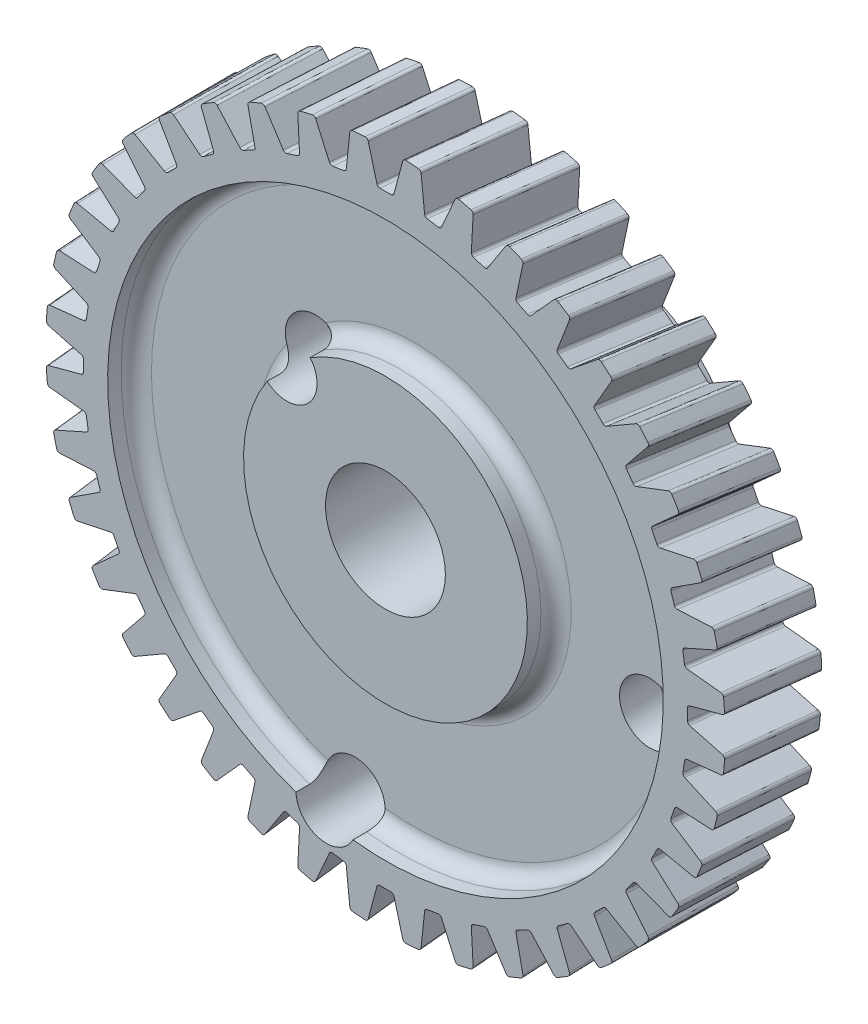
SolidWorks part; units mm, degrees
ref_plane "Front Plane" through (0, 0, 0) normal (0, 0, 1) x (1, 0, 0)
ref_plane "Top Plane" through (0, 0, 0) normal (0, 1, 0) x (1, 0, 0)
ref_plane "Right Plane" through (0, 0, 0) normal (1, 0, 0) x (0, 0, -1)
sketch "Sketch2" plane through (0, 0, 0) normal (1, 0, 0) x (0, 0, -1)
  line L0 (0, 0) -> (0, 22.5) construction
  line L1 (11, 3.9688) -> (-3.2, 3.9687)
  line L2 (-3.2, 3.9687) -> (-3.2, 9.4)
  line L3 (-3.2, 9.4) -> (-1.3, 9.4)
  line L4 (-1.3, 9.4) -> (-1.3, 18.4)
  line L5 (-1.3, 18.4) -> (-3.2, 18.4)
  line L6 (-3.2, 18.4) -> (-3.2, 22.5)
  line L7 (-3.2, 22.5) -> (3.2, 22.5)
  line L8 (3.2, 18.4) -> (3.2, 22.5)
  line L9 (1.3, 18.4) -> (3.2, 18.4)
  line L10 (1.3, 9.4) -> (1.3, 18.4)
  line L11 (3.2, 9.4) -> (1.3, 9.4)
  line L12 (3.2, 9.4) -> (11, 9.4)
  line L13 (11, 9.4) -> (11, 3.9688)
  line L14 (0, 0) -> (14.174, 0) construction
  dimension "D1" = 14.2
  dimension "D2" = 3.2
  dimension "D3" = 4.5
  dimension "D4" = 7.9375
  dimension "D5" = 9.4
  dimension "D6" = 9
  dimension "D7" = 22.5
  dimension "D8" = 6.4
revolve "Revolve1" add sketch "Sketch2" angle 360 about L14
fillet "Fillet1" radius 1 4 edges at (18.4, 0, 1.3) (9.4, 0, 1.3) (9.4, 0, -1.3) (18.4, 0, -1.3)
sketch "Sketch3" plane through (0, 0, 3.2) normal (0, 0, 1) x (1, 0, 0)
  line L0 (0, 22.6922) -> (0, 20) construction
  line L1 (-0.525, 20) -> (0.525, 20)
  line L2 (0.525, 20) -> (1.2464, 22.6922)
  line L3 (1.2464, 22.6922) -> (-1.2464, 22.6922)
  line L4 (-0.525, 20) -> (-1.2464, 22.6922)
  dimension "D1" = 20
  dimension "D2" = 1.05
  dimension "D3" = 15
sketch "Sketch4" plane through (0, 0, 0) normal (0, 1, 0) x (1, 0, 0)
  line L0 (0, -3.2) -> (0.691, 3.2)
  line L1 (1.2464, -3.2) -> (-1.2464, -3.2) construction
  line L2 (22.5, 3.2) -> (-22.5, 3.2) construction
sweep "Cut-Sweep1" cut profiles "Sketch3" path "Sketch4"
pattern_circular "CirPattern1" count 40 over 360 about axis through (0, 0, 3.2) along (0, 0, 1) of "Cut-Sweep1"
fillet "Fillet2" radius 0.2 160 edges at (1.526, 22.4482, 0.0047) (0.8705, 20, 0) (-0.8445, 22.4841, -0.0056) (-2.0045, 22.4105, 0.0047) (-2.2689, 19.8899, 0) (-3.306, 19.7257, 0) (-4.3514, 22.0752, -0.0056) (-5.4856, 21.8211, 0.0047) (-5.3525, 19.2901, 0) (-6.3511, 18.9657, 0) (-7.7512, 21.1227, -0.0056) (-8.8316, 20.6943, 0.0047) (-8.3042, 18.2153, 0) (-9.2398, 17.7386, 0) (-10.9601, 19.6501, -0.0056) (-11.9602, 19.0579, 0.0047) (-11.0515, 16.692, 0) (-11.9009, 16.0748, 0) (-13.8991, 17.6936, -0.0056) (-14.7943, 16.9523, 0.0047) (-13.5266, 14.7577, 0) (-14.2691, 14.0152, 0) (-16.4959, 15.3015, -0.0056) (-17.264, 14.4292, 0.0047) (-15.6687, 12.4599, 0) (-16.2859, 11.6105, 0) (-18.6865, 12.5326, -0.0056) (-19.3087, 11.5509, 0.0047) (-17.4249, 9.8554, 0) (-17.9016, 8.9199, 0) (-20.4169, 9.4551, -0.0056) (-20.878, 8.3882, 0.0047) (-18.7521, 7.0082, 0) (-19.0766, 6.0096, 0) (-21.6447, 6.1448, -0.0056) (-21.9331, 5.0188, 0.0047) (-19.6176, 3.9885, 0) (-19.7818, 2.9514, 0) (-22.3394, 2.6832, -0.0056) (-22.4482, 1.526, 0.0047) (-20, 0.8705, 0) (-20, -0.1795, 0) (-22.4841, -0.8445, -0.0056) (-22.4105, -2.0045, 0.0047) (-19.8899, -2.2689, 0) (-19.7257, -3.306, 0) (-22.0752, -4.3514, -0.0056) (-21.8211, -5.4856, 0.0047) (-19.2901, -5.3525, 0) (-18.9657, -6.3511, 0) (-21.1227, -7.7512, -0.0056) (-20.6943, -8.8316, 0.0047) (-18.2153, -8.3042, 0) (-17.7386, -9.2398, 0) (-19.6501, -10.9601, -0.0056) (-19.0579, -11.9602, 0.0047) (-16.692, -11.0515, 0) (-16.0748, -11.9009, 0) (-17.6936, -13.8991, -0.0056) (-16.9523, -14.7943, 0.0047) (-14.7577, -13.5266, 0) (-14.0152, -14.2691, 0) (-15.3015, -16.4959, -0.0056) (-14.4292, -17.264, 0.0047) (-12.4599, -15.6687, 0) (-11.6105, -16.2859, 0) (-12.5326, -18.6865, -0.0056) (-11.5509, -19.3087, 0.0047) (-9.8554, -17.4249, 0) (-8.9199, -17.9016, 0) (-9.4551, -20.4169, -0.0056) (-8.3882, -20.878, 0.0047) (-7.0082, -18.7521, 0) (-6.0096, -19.0766, 0) (-6.1448, -21.6447, -0.0056) (-5.0188, -21.9331, 0.0047) (-3.9885, -19.6176, 0) (-2.9514, -19.7818, 0) (-2.6832, -22.3394, -0.0056) (-1.526, -22.4482, 0.0047) (-0.8705, -20, 0) (0.1795, -20, 0) (0.8445, -22.4841, -0.0056) (2.0045, -22.4105, 0.0047) (2.2689, -19.8899, 0) (3.306, -19.7257, 0) (4.3514, -22.0752, -0.0056) (5.4856, -21.8211, 0.0047) (5.3525, -19.2901, 0) (6.3511, -18.9657, 0) (7.7512, -21.1227, -0.0056) (8.8316, -20.6943, 0.0047) (8.3042, -18.2153, 0) (9.2398, -17.7386, 0) (10.9601, -19.6501, -0.0056) (11.9602, -19.0579, 0.0047) (11.0515, -16.692, 0) (11.9009, -16.0748, 0) (13.8991, -17.6936, -0.0056) (14.7943, -16.9523, 0.0047) (13.5266, -14.7577, 0) (14.2691, -14.0152, 0) (16.4959, -15.3015, -0.0056) (17.264, -14.4292, 0.0047) (15.6687, -12.4599, 0) (16.2859, -11.6105, 0) (18.6865, -12.5326, -0.0056) (19.3087, -11.5509, 0.0047) (17.4249, -9.8554, 0) (17.9016, -8.9199, 0) (20.4169, -9.4551, -0.0056) (20.878, -8.3882, 0.0047) (18.7521, -7.0082, 0) (19.0766, -6.0096, 0) (21.6447, -6.1448, -0.0056) (21.9331, -5.0188, 0.0047) (19.6176, -3.9885, 0) (19.7818, -2.9514, 0) (22.3394, -2.6832, -0.0056) (22.4482, -1.526, 0.0047) (20, -0.8705, 0) (20, 0.1795, 0) (22.4841, 0.8445, -0.0056) (22.4105, 2.0045, 0.0047) (19.8899, 2.2689, 0) (19.7257, 3.306, 0) (22.0752, 4.3514, -0.0056) (21.8211, 5.4856, 0.0047) (19.2901, 5.3525, 0) (18.9657, 6.3511, 0) (21.1227, 7.7512, -0.0056) (20.6943, 8.8316, 0.0047) (18.2153, 8.3042, 0) (17.7386, 9.2398, 0) (19.6501, 10.9601, -0.0056) (19.0579, 11.9602, 0.0047) (16.692, 11.0515, 0) (16.0748, 11.9009, 0) (17.6936, 13.8991, -0.0056) (16.9523, 14.7943, 0.0047) (14.7577, 13.5266, 0) (14.0152, 14.2691, 0) (15.3015, 16.4959, -0.0056) (14.4292, 17.264, 0.0047) (12.4599, 15.6687, 0) (11.6105, 16.2859, 0) (12.5326, 18.6865, -0.0056) (11.5509, 19.3087, 0.0047) (9.8554, 17.4249, 0) (8.9199, 17.9016, 0) (9.4551, 20.4169, -0.0056) (8.3882, 20.878, 0.0047) (7.0082, 18.7521, 0) (6.0096, 19.0766, 0) (6.1448, 21.6447, -0.0056) (5.0188, 21.9331, 0.0047) (3.9885, 19.6176, 0) (2.9514, 19.7818, 0) (2.6832, 22.3394, -0.0056) (-0.1795, 20, 0)
ref_axis "gear axis" through (0, 0, -11) along (0, 0, 1)
hole_wizard "Ø4.0 (4) Diameter Hole1" positions "Sketch5" profile "Sketch6" hole size "Ø4.0" standard "ISO" end condition through all
sketch "Sketch5" plane through (66.6178, -178.24, 3.9366) normal (0, 0, 1) x (1, -0.0054, 0)
  circle A5 centre (-65.8366, 173.3131) radius 13.9687
  point P0 (-74.1426, 184.5441)
  point P2 (-51.9572, 174.8908)
  point P4 (-71.41, 160.5044)
sketch "Sketch6" plane through (-6.5298, 6.7008, 3.9366) normal (1, 0, 0) x (0, -1, 0)
  line L0 (0, 0) -> (0, 14.9366)
  line L1 (0, 14.9366) -> (2, 14.9366)
  line L2 (2, 14.9366) -> (2, 0)
  line L3 (2, 0) -> (0, 0)
  line L4 (0, -6.35) -> (0, 107.95) construction
  dimension "Thru Hole Dia." = 4
  dimension "Thru Hole Depth" = 14.9366
